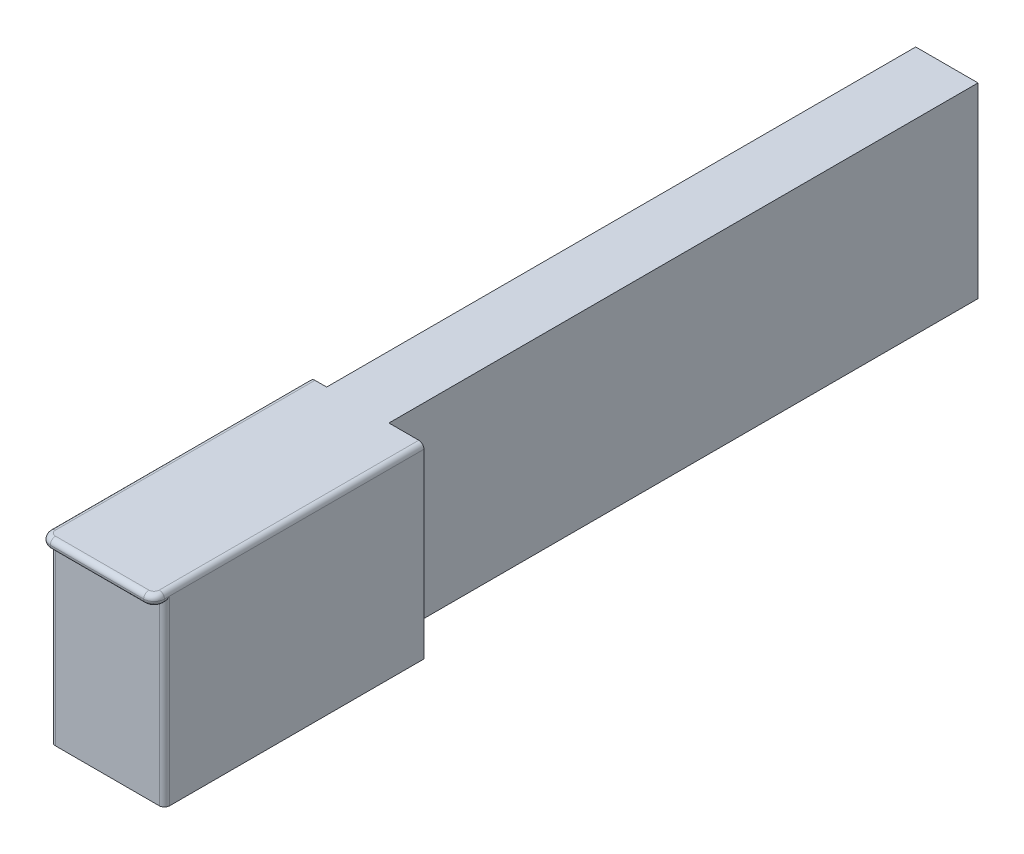
SolidWorks part; units mm, degrees
ref_plane "Front Plane" through (0, 0, 0) normal (0, 0, 1) x (1, 0, 0)
ref_plane "Top Plane" through (0, 0, 0) normal (0, 1, 0) x (1, 0, 0)
ref_plane "Right Plane" through (0, 0, 0) normal (1, 0, 0) x (0, 0, -1)
sketch "Sketch1" plane through (0, 0, 0) normal (0, 1, 0) x (1, 0, 0)
  line L1 (-11, -81.75) -> (11, -81.75)
  line L2 (-11, -81.75) -> (-11, 81.75)
  line L3 (-11, 81.75) -> (11, 81.75)
  line L4 (11, -81.75) -> (11, 81.75)
  line L5 (-11, -81.75) -> (11, 81.75) construction
  line L6 (-11, 81.75) -> (11, -81.75) construction
  point P0 (0, 0)
  dimension "D1" = 163.5
  dimension "D2" = 22
extrude "Boss-Extrude1" add sketch "Sketch1" along normal blind 36 contours L2 L3 L4 L1
fillet "Fillet1" radius 1 2 edges at (-11, 18, 81.75) (11, 18, 81.75)
sketch "Sketch2" plane through (0, 36, 0) normal (0, 1, 0) x (1, 0, 0)
  line L0 (11, -80.75) -> (11, 81.75) construction
  line L1 (-11, 81.75) -> (11, 81.75)
  line L2 (-11, 81.75) -> (-11, -83.75)
  line L3 (-11, -83.75) -> (11, -83.75)
  line L4 (11, 81.75) -> (11, -83.75)
  line L5 (-10, -81.75) -> (10, -81.75) construction
  dimension "D1" = 2
extrude "Boss-Extrude2" add sketch "Sketch2" against normal blind 2
fillet "Fillet2" radius 2 2 edges at (-11, 35, 83.75) (11, 35, 83.75)
fillet "Fillet3" radius 1 10 edges at (-11, 34, 81.25) (-10.4142, 34, 83.1642) (11, 34, 81.25) (10.4142, 34, 83.1642) (11, 36, 0) (10.4142, 36, 83.1642) (0, 36, 83.75) (-10.4142, 36, 83.1642) (-11, 36, 0) (0, 34, 83.75)
sketch "Sketch3" plane through (0, 36, 0) normal (0, 1, 0) x (1, 0, 0)
  line L1 (7.5, -31.75) -> (11, -31.75)
  line L2 (7.5, -31.75) -> (7.5, 81.75)
  line L3 (7.5, 81.75) -> (11, 81.75)
  line L4 (11, -31.75) -> (11, 81.75)
  line L5 (7.5, -31.75) -> (11, 81.75) construction
  line L6 (7.5, 81.75) -> (11, -31.75) construction
  line L7 (-10, -81.75) -> (10, -81.75) construction
  line L8 (-11, 81.75) -> (11, 81.75) construction
  line L9 (11, 81.75) -> (11, -80.75) construction
  dimension "D1" = 3.5
  dimension "D2" = 50
extrude "Cut-Extrude2" [suppressed] cut sketch "Sketch3" against normal through all
sketch "Sketch5" plane through (-11, 0, 0) normal (-1, 0, 0) x (0, 0, 1)
  line L0 (81.75, 34) -> (81.75, 0) construction
  line L1 (80.75, 0) -> (-81.75, 0) construction
  line L2 (-81.75, 36) -> (81.75, 36) construction
  line L3 (-81.75, 35) -> (-81.75, 0) construction
  line L8 (31.75, 36) -> (-81.75, 36)
  line L9 (31.75, 0) -> (31.75, 36)
  line L10 (-81.75, 0) -> (31.75, 0)
  line L11 (-81.75, 36) -> (-81.75, 0)
  dimension "D1" = 50
extrude "Cut-Extrude4" [suppressed] cut sketch "Sketch5" against normal blind 3.5
sketch "Sketch4" [suppressed] plane through (7.5, 0, 0) normal (1, 0, 0) x (0, 0, -1)
  line L4 (81.75, 36) -> (-31.75, 36)
  line L5 (-31.75, 36) -> (-31.75, 0)
  line L6 (-31.75, 0) -> (81.75, 0)
  line L7 (81.75, 0) -> (81.75, 36)
  line L8 (81.75, 36) -> (-31.75, 36)
  line L9 (-31.75, 36) -> (-31.75, 0)
  line L10 (-31.75, 0) -> (81.75, 0)
  line L11 (81.75, 0) -> (81.75, 36)
  dimension "D1" = 0
extrude "Cut-Extrude3" [suppressed] cut sketch "Sketch4" against normal blind 3.25
sketch "Sketch6" [suppressed] plane through (-7.5, 0, 0) normal (-1, 0, 0) x (0, 0, 1)
  line L4 (-81.75, 36) -> (-81.75, 0)
  line L5 (-81.75, 0) -> (31.75, 0)
  line L6 (31.75, 0) -> (31.75, 36)
  line L7 (31.75, 36) -> (-81.75, 36)
  line L8 (-81.75, 36) -> (-81.75, 0)
  line L9 (-81.75, 0) -> (31.75, 0)
  line L10 (31.75, 0) -> (31.75, 36)
  line L11 (31.75, 36) -> (-81.75, 36)
  dimension "D1" = 0
extrude "Cut-Extrude5" [suppressed] cut sketch "Sketch6" against normal blind 3.25
sketch "White" plane through (0, 0, 0) normal (0, 1, 0) x (1, 0, 0)
  line L0 (12.5, -81.75) -> (34.5, -81.75)
  line L1 (-11, -81.75) -> (11, -81.75)
  line L2 (-11, -81.75) -> (-11, 81.75)
  line L3 (-11, 81.75) -> (11, 81.75)
  line L4 (11, -81.75) -> (11, 81.75)
  line L5 (12.5, -81.75) -> (12.5, 81.75)
  line L6 (12.5, 81.75) -> (34.5, 81.75)
  line L7 (34.5, -81.75) -> (34.5, 81.75)
  line L8 (36, -81.75) -> (58, -81.75)
  line L9 (36, -81.75) -> (36, 81.75)
  line L10 (36, 81.75) -> (58, 81.75)
  line L11 (58, -81.75) -> (58, 81.75)
  line L12 (59.5, -81.75) -> (81.5, -81.75)
  line L13 (59.5, -81.75) -> (59.5, 81.75)
  line L14 (59.5, 81.75) -> (81.5, 81.75)
  line L15 (81.5, -81.75) -> (81.5, 81.75)
  line L16 (83, -81.75) -> (105, -81.75)
  line L17 (83, -81.75) -> (83, 81.75)
  line L18 (83, 81.75) -> (105, 81.75)
  line L19 (105, -81.75) -> (105, 81.75)
  line L20 (106.5, -81.75) -> (128.5, -81.75)
  line L21 (106.5, -81.75) -> (106.5, 81.75)
  line L22 (106.5, 81.75) -> (128.5, 81.75)
  line L23 (128.5, -81.75) -> (128.5, 81.75)
  line L24 (130, -81.75) -> (152, -81.75)
  line L25 (130, -81.75) -> (130, 81.75)
  line L26 (130, 81.75) -> (152, 81.75)
  line L27 (152, -81.75) -> (152, 81.75)
  dimension "D1" = 7
sketch "Black" plane through (0, 0, 0) normal (0, 1, 0) x (1, 0, 0)
  line L0 (-11, 81.75) -> (11, 81.75) construction
  line L1 (16, -31.75) -> (4, -31.75)
  line L2 (16, -31.75) -> (16, 81.75)
  line L3 (16, 81.75) -> (4, 81.75)
  line L4 (4, -31.75) -> (4, 81.75)
  line L6 (31, -31.75) -> (43, -31.75)
  line L7 (31, -31.75) -> (31, 81.75)
  line L8 (31, 81.75) -> (43, 81.75)
  line L9 (43, -31.75) -> (43, 81.75)
  line L10 (12.5, -81.75) -> (34.5, -81.75) construction
  line L11 (16, -31.75) -> (31, -31.75) construction
  line L12 (36, 81.75) -> (58, 81.75) construction
  line L13 (106.5, 81.75) -> (128.5, 81.75) construction
  line L14 (111.75, 81.75) -> (99.75, 81.75)
  line L15 (111.75, 81.75) -> (111.75, -31.75)
  line L16 (111.75, -31.75) -> (99.75, -31.75)
  line L17 (99.75, 81.75) -> (99.75, -31.75)
  line L18 (83, 81.75) -> (105, 81.75) construction
  line L19 (126.75, 81.75) -> (138.75, 81.75)
  line L20 (126.75, 81.75) -> (126.75, -31.75)
  line L21 (126.75, -31.75) -> (138.75, -31.75)
  line L22 (138.75, 81.75) -> (138.75, -31.75)
  line L23 (84.75, 81.75) -> (72.75, 81.75)
  line L24 (84.75, 81.75) -> (84.75, -31.75)
  line L25 (84.75, -31.75) -> (72.75, -31.75)
  line L26 (72.75, 81.75) -> (72.75, -31.75)
  line L27 (105, -81.75) -> (106.5, -81.75) construction
  point P14 (23.5, -81.75)
  point P15 (23.5, -31.75)
  point P36 (105.75, -81.75)
  point P37 (105.75, -31.75)
  dimension "D1" = 50
  dimension "D2" = 12
  dimension "D3" = 12
  dimension "D4" = 15
  dimension "D5" = 15
  dimension "D6" = 15
sketch "Sketch11" plane through (0, 36, 0) normal (0, 1, 0) x (1, 0, 0)
  line L1 (11, 81.75) -> (2.5, 81.75)
  line L2 (11, 81.75) -> (11, -31.75)
  line L3 (11, -31.75) -> (2.5, -31.75)
  line L4 (2.5, 81.75) -> (2.5, -31.75)
  line L5 (16, -31.75) -> (4, -31.75) construction
  dimension "D1" = 8.5
extrude "C" [suppressed] cut sketch "Sketch11" against normal through all
sketch "Sketch12" plane through (0, 36, 0) normal (0, 1, 0) x (1, 0, 0)
  line L0 (31, -31.75) -> (43, -31.75) construction
  line L1 (-11, 81.75) -> (-6, 81.75)
  line L2 (-11, 81.75) -> (-11, -31.75)
  line L3 (-11, -31.75) -> (-6, -31.75)
  line L4 (-6, 81.75) -> (-6, -31.75)
  line L5 (11, 81.75) -> (6, 81.75)
  line L6 (11, 81.75) -> (11, -31.75)
  line L7 (11, -31.75) -> (6, -31.75)
  line L8 (6, 81.75) -> (6, -31.75)
  dimension "D1" = 5
  dimension "D2" = 5
extrude "D" [suppressed] cut sketch "Sketch12" against normal through all
sketch "Sketch13" plane through (0, 36, 0) normal (0, 1, 0) x (1, 0, 0)
  line L1 (-11, 81.75) -> (-2.5, 81.75)
  line L2 (-11, 81.75) -> (-11, -31.75)
  line L3 (-11, -31.75) -> (-2.5, -31.75)
  line L4 (-2.5, 81.75) -> (-2.5, -31.75)
  line L5 (16, -31.75) -> (4, -31.75) construction
  dimension "D1" = 8.5
extrude "E" [suppressed] cut sketch "Sketch13" against normal through all
sketch "Sketch14" plane through (0, 36, 0) normal (0, 1, 0) x (1, 0, 0)
  line L0 (16, -31.75) -> (4, -31.75) construction
  line L1 (11, 81.75) -> (0.75, 81.75)
  line L2 (11, 81.75) -> (11, -31.75)
  line L3 (11, -31.75) -> (0.75, -31.75)
  line L4 (0.75, 81.75) -> (0.75, -31.75)
  dimension "D1" = 10.25
extrude "F" [suppressed] cut sketch "Sketch14" against normal through all
sketch "Sketch15" plane through (0, 36, 0) normal (0, 1, 0) x (1, 0, 0)
  line L1 (-11, 81.75) -> (-7.75, 81.75)
  line L2 (-11, 81.75) -> (-11, -31.75)
  line L3 (-11, -31.75) -> (-7.75, -31.75)
  line L4 (-7.75, 81.75) -> (-7.75, -31.75)
  line L5 (11, 81.75) -> (4.25, 81.75)
  line L6 (11, 81.75) -> (11, -31.75)
  line L7 (11, -31.75) -> (4.25, -31.75)
  line L8 (4.25, 81.75) -> (4.25, -31.75)
  line L9 (16, -31.75) -> (4, -31.75) construction
  dimension "D1" = 3.25
  dimension "D2" = 6.75
extrude "G" cut sketch "Sketch15" against normal through all
sketch "Sketch16" plane through (0, 36, 0) normal (0, 1, 0) x (1, 0, 0)
  line L0 (16, -31.75) -> (4, -31.75) construction
  line L1 (-11, 81.75) -> (-4.25, 81.75)
  line L2 (-11, 81.75) -> (-11, -31.75)
  line L3 (-11, -31.75) -> (-4.25, -31.75)
  line L4 (-4.25, 81.75) -> (-4.25, -31.75)
  line L5 (11, 81.75) -> (7.75, 81.75)
  line L6 (11, 81.75) -> (11, -31.75)
  line L7 (11, -31.75) -> (7.75, -31.75)
  line L8 (7.75, 81.75) -> (7.75, -31.75)
  dimension "D1" = 6.75
  dimension "D2" = 3.25
extrude "A" [suppressed] cut sketch "Sketch16" against normal through all
sketch "Sketch17" plane through (0, 36, 0) normal (0, 1, 0) x (1, 0, 0)
  line L0 (16, -31.75) -> (4, -31.75) construction
  line L1 (-11, 81.75) -> (-0.75, 81.75)
  line L2 (-11, 81.75) -> (-11, -31.75)
  line L3 (-11, -31.75) -> (-0.75, -31.75)
  line L4 (-0.75, 81.75) -> (-0.75, -31.75)
  dimension "D1" = 10.25
extrude "B" [suppressed] cut sketch "Sketch17" against normal through all
